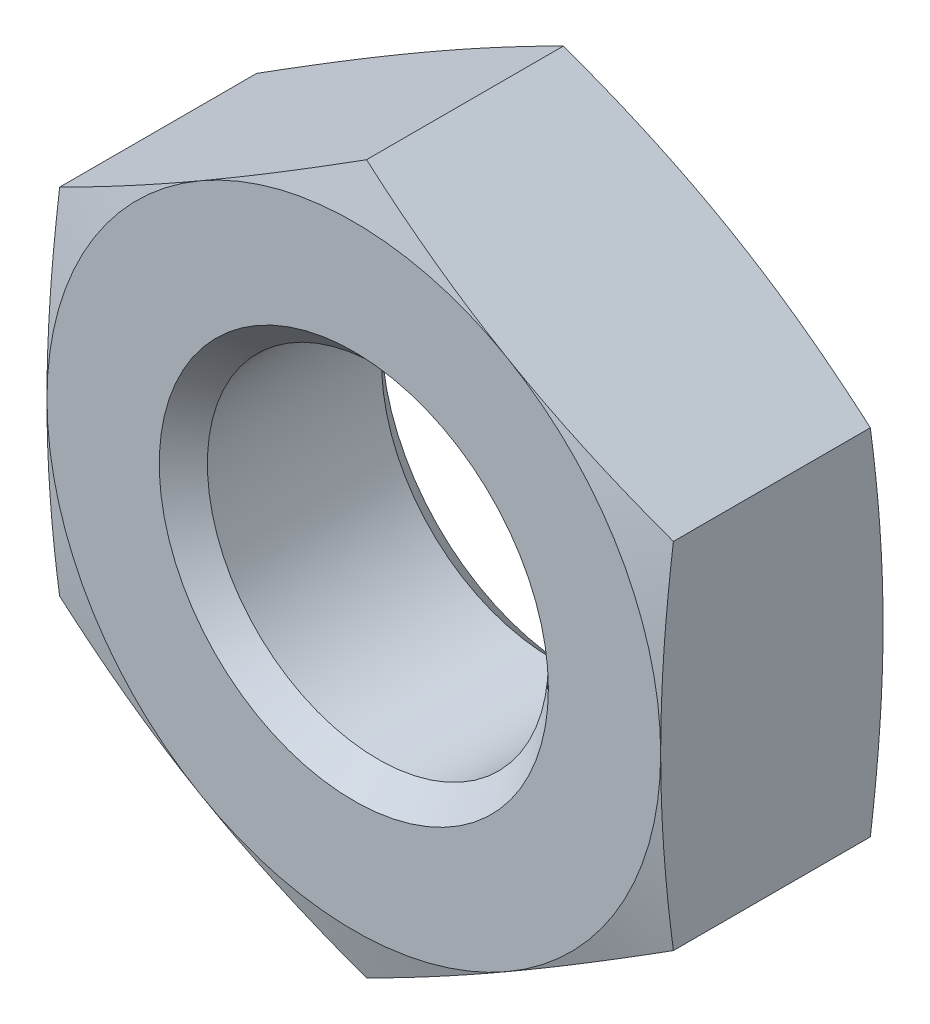
SolidWorks part; units mm, degrees
material "Cast Alloy Steel"
ref_plane "Front Plane" through (0, 0, 0) normal (0, 0, 1) x (1, 0, 0)
ref_plane "Top Plane" through (0, 0, 0) normal (0, 1, 0) x (1, 0, 0)
ref_plane "Right Plane" through (0, 0, 0) normal (1, 0, 0) x (0, 0, -1)
sketch "Sketch1" plane through (0, 0, 0) normal (1, 0, 0) x (0, 0, -1)
  line L0 (0, 0) -> (0, 8.763)
  line L1 (0, 8.763) -> (0.4696, 10.5156)
  line L2 (0.4696, 10.5156) -> (5.8804, 10.5156)
  line L3 (5.8804, 10.5156) -> (6.35, 8.763)
  line L4 (6.35, 8.763) -> (6.35, 0)
  line L5 (6.35, 0) -> (0, 0)
  line L6 (6.35, 0) -> (0, 0) construction
sketch "Sketch2" plane through (0, 0, 0) normal (0, 0, 1) x (1, 0, 0)
  line L0 (-17.526, 17.526) -> (-17.526, -17.526)
  line L1 (-17.526, -17.526) -> (17.526, -17.526)
  line L2 (17.526, -17.526) -> (17.526, 17.526)
  line L3 (17.526, 17.526) -> (-17.526, 17.526)
  line L4 (-8.763, 5.0593) -> (-8.763, -5.0593)
  line L5 (-8.763, -5.0593) -> (0, -10.1186)
  line L6 (0, -10.1186) -> (8.763, -5.0593)
  line L7 (8.763, -5.0593) -> (8.763, 5.0593)
  line L8 (8.763, 5.0593) -> (0, 10.1186)
  line L9 (0, 10.1186) -> (-8.763, 5.0593)
revolve "Revolve1" add sketch "Sketch1" angle 360 about L6 reverse direction yes
extrude "Cut-Extrude1" cut sketch "Sketch2" against normal blind 6.35
sketch "Sketch3" plane through (0, 0, 0) normal (1, 0, 0) x (0, 0, -1)
  line L0 (0, 0) -> (0, 5.5563)
  line L1 (0, 5.5563) -> (0.6871, 4.8692)
  line L2 (0.6871, 4.8692) -> (5.6629, 4.8692)
  line L3 (5.6629, 4.8692) -> (6.35, 5.5563)
  line L4 (6.35, 5.5563) -> (6.35, 0)
  line L5 (6.35, 0) -> (0, 0)
  line L6 (6.35, 0) -> (0, 0) construction
revolve "Cut-Revolve1" cut sketch "Sketch3" angle 360 about L6 reverse direction yes
cosmetic thread "Cosmetic Thread1" parameters "D1"=6.35, "D2"=11.1125
ref_plane "NUT XY" through (0, 0, 0) normal (0, 0, 1) x (1, 0, 0)
ref_plane "NUT XZ" through (0, 0, 0) normal (0, -1, 0) x (-1, 0, 0)
ref_plane "NUT YZ" through (0, 0, 0) normal (1, 0, 0) x (0, 0, -1)
ref_axis "NUT X" through (-80.9, 0, 0) along (1, 0, 0)
ref_axis "NUT Y" through (0, -50, 0) along (0, 1, 0)
ref_axis "NUT Z" through (0, 0, 80.9) along (0, 0, -1)
sketch3d "NUT"
  point P0 (0, 0, 0)
ref_plane "a1 XY" through (0, 0, 0) normal (0, 0, 1) x (1, 0, 0)
ref_plane "a1 XZ" through (0, 8.763, 0) normal (0, -1, 0) x (-1, 0, 0)
ref_plane "a1 YZ" through (-8.763, 0, 0) normal (1, 0, 0) x (0, 0, -1)
ref_axis "a1 X" through (-80.9, 8.763, 0) along (1, 0, 0)
ref_axis "a1 Y" through (-8.763, -50, 0) along (0, 1, 0)
ref_axis "a1 Z" through (-8.763, 8.763, 80.9) along (0, 0, -1)
sketch3d "a1"
  point P0 (-8.763, 8.763, 0)
ref_plane "a2 XY" through (0, 0, 0) normal (0, 0, 1) x (1, 0, 0)
ref_plane "a2 XZ" through (0, 8.763, 0) normal (0, -1, 0) x (-1, 0, 0)
ref_plane "a2 YZ" through (8.763, 0, 0) normal (1, 0, 0) x (0, 0, -1)
ref_axis "a2 X" through (-80.9, 8.763, 0) along (1, 0, 0)
ref_axis "a2 Y" through (8.763, -50, 0) along (0, 1, 0)
ref_axis "a2 Z" through (8.763, 8.763, 80.9) along (0, 0, -1)
sketch3d "a2"
  point P0 (8.763, 8.763, 0)
ref_plane "b1 XY" through (0, 0, 0) normal (1, 0, 0) x (0, 0, -1)
ref_plane "b1 XZ" through (0, 8.763, 0) normal (0, -1, 0) x (-1, 0, 0)
ref_plane "b1 YZ" through (0, 0, 0) normal (0, 0, -1) x (-1, 0, 0)
ref_axis "b1 X" through (0, 8.763, 80.9) along (0, 0, -1)
ref_axis "b1 Y" through (0, -50, 0) along (0, 1, 0)
ref_axis "b1 Z" through (80.9, 8.763, 0) along (-1, 0, 0)
sketch3d "b1"
  point P0 (0, 8.763, 0)
ref_plane "b2 XY" through (0, 0, 0) normal (1, 0, 0) x (0, 0, -1)
ref_plane "b2 XZ" through (0, 8.763, 0) normal (0, -1, 0) x (-1, 0, 0)
ref_plane "b2 YZ" through (0, 0, -6.35) normal (0, 0, -1) x (-1, 0, 0)
ref_axis "b2 X" through (0, 8.763, 80.9) along (0, 0, -1)
ref_axis "b2 Y" through (0, -50, -6.35) along (0, 1, 0)
ref_axis "b2 Z" through (80.9, 8.763, -6.35) along (-1, 0, 0)
sketch3d "b2"
  point P0 (0, 8.763, -6.35)
ref_plane "e XY" through (0, 0, 0) normal (1, 0, 0) x (0, 0, -1)
ref_plane "e XZ" through (0, 0, 0) normal (0, -1, 0) x (-1, 0, 0)
ref_plane "e YZ" through (0, 0, -6.35) normal (0, 0, -1) x (-1, 0, 0)
ref_axis "e X" through (0, 0, 80.9) along (0, 0, -1)
ref_axis "e Y" through (0, -50, -6.35) along (0, 1, 0)
ref_axis "e Z" through (80.9, 0, -6.35) along (-1, 0, 0)
sketch3d "e"
  point P0 (0, 0, -6.35)
ref_plane "ol1 XY" through (0, 0, 0) normal (0, 1, 0) x (1, 0, 0)
ref_plane "ol1 XZ" through (0, 0, -8.763) normal (0, 0, 1) x (1, 0, 0)
ref_plane "ol1 YZ" through (0, 0, 0) normal (1, 0, 0) x (0, 0, -1)
ref_axis "ol1 X" through (-80.9, 0, -8.763) along (1, 0, 0)
ref_axis "ol1 Y" through (0, 0, 50) along (0, 0, -1)
ref_axis "ol1 Z" through (0, 50, -8.763) along (0, -1, 0)
sketch3d "ol1"
  point P0 (0, 0, -8.763)
ref_plane "ol2 XY" through (0, 0, 0) normal (0, 1, 0) x (1, 0, 0)
ref_plane "ol2 XZ" through (0, 0, -8.763) normal (0, 0, 1) x (1, 0, 0)
ref_plane "ol2 YZ" through (6.35, 0, 0) normal (1, 0, 0) x (0, 0, -1)
ref_axis "ol2 X" through (-80.9, 0, -8.763) along (1, 0, 0)
ref_axis "ol2 Y" through (6.35, 0, 50) along (0, 0, -1)
ref_axis "ol2 Z" through (6.35, 50, -8.763) along (0, -1, 0)
sketch3d "ol2"
  point P0 (6.35, 0, -8.763)
ref_plane "th1 XY" through (0, 0, 0) normal (1, 0, 0) x (0, 0, -1)
ref_plane "th1 XZ" through (0, 5.5563, 0) normal (0, -1, 0) x (-1, 0, 0)
ref_plane "th1 YZ" through (0, 0, -6.35) normal (0, 0, -1) x (-1, 0, 0)
ref_axis "th1 X" through (0, 5.5563, 80.9) along (0, 0, -1)
ref_axis "th1 Y" through (0, -50, -6.35) along (0, 1, 0)
ref_axis "th1 Z" through (80.9, 5.5563, -6.35) along (-1, 0, 0)
sketch3d "th1"
  point P0 (0, 5.5563, -6.35)
ref_plane "th2 XY" through (0, 0, 0) normal (1, 0, 0) x (0, 0, -1)
ref_plane "th2 XZ" through (0, -5.5563, 0) normal (0, -1, 0) x (-1, 0, 0)
ref_plane "th2 YZ" through (0, 0, -6.35) normal (0, 0, -1) x (-1, 0, 0)
ref_axis "th2 X" through (0, -5.5563, 80.9) along (0, 0, -1)
ref_axis "th2 Y" through (0, -50, -6.35) along (0, 1, 0)
ref_axis "th2 Z" through (80.9, -5.5563, -6.35) along (-1, 0, 0)
sketch3d "th2"
  point P0 (0, -5.5563, -6.35)
